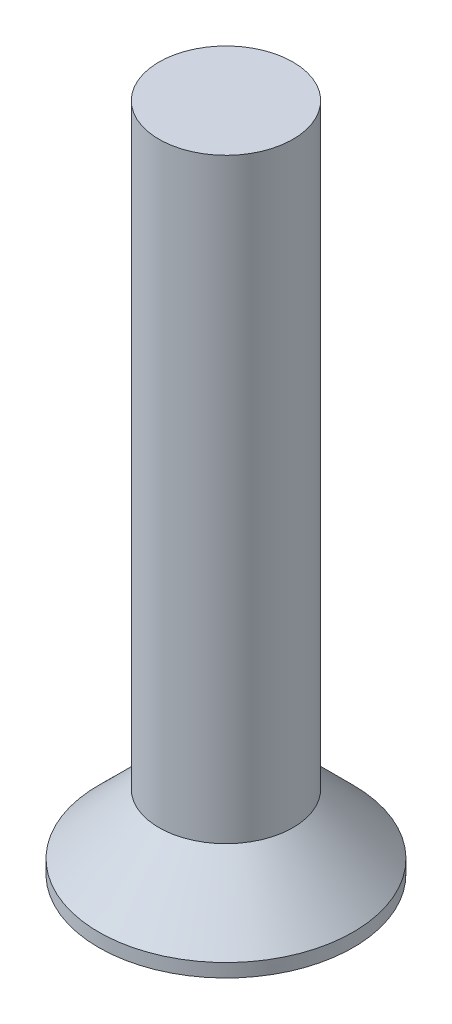
SolidWorks part; units mm, degrees
material "Nylon 101"
ref_plane "Front Plane" through (0, 0, 0) normal (0, 0, 1) x (1, 0, 0)
ref_plane "Top Plane" through (0, 0, 0) normal (0, 1, 0) x (1, 0, 0)
ref_plane "Right Plane" through (0, 0, 0) normal (1, 0, 0) x (0, 0, -1)
sketch "Sketch1" plane through (0, 0, 0) normal (0, 1, 0) x (1, 0, 0)
  circle A0 centre (0, 0) radius 1.9
  dimension "D1" = 3.8
extrude "Boss-Extrude1" add sketch "Sketch1" along normal blind 1.3
sketch "Sketch2" plane through (0, 0, 0) normal (0, -1, 0) x (1, 0, 0)
  circle A0 centre (0, 0) radius 1
  dimension "D1" = 2
extrude "Boss-Extrude2" add sketch "Sketch2" against normal blind 10
chamfer "Chamfer1" distance 1.1 angle 45 1 edges at (0, 1.3, 1.9)
sketch "Sketch3" plane through (0, 0, 0) normal (0, -1, 0) x (1, 0, 0)
  line L0 (-0.25, 1.5) -> (-0.25, 0.25)
  line L1 (1.5, -0.25) -> (-1.5, -0.25) construction
  line L2 (1.5, -0.25) -> (1.5, 0.25) construction
  line L3 (1.5, 0.25) -> (-1.5, 0.25) construction
  line L4 (-1.5, -0.25) -> (-1.5, 0.25) construction
  line L5 (1.5, -0.25) -> (-1.5, 0.25) construction
  line L6 (1.5, 0.25) -> (-1.5, -0.25) construction
  line L7 (-0.25, -1.5) -> (0.25, -1.5) construction
  line L8 (-0.25, -1.5) -> (-0.25, 1.5) construction
  line L9 (-0.25, 1.5) -> (0.25, 1.5) construction
  line L10 (0.25, -1.5) -> (0.25, 1.5) construction
  line L11 (-0.25, -1.5) -> (0.25, 1.5) construction
  line L12 (-0.25, 1.5) -> (0.25, -1.5) construction
  line L13 (-0.25, 0.25) -> (-1.5, 0.25)
  line L14 (-1.5, 0.25) -> (-1.5, -0.25)
  line L15 (-1.5, -0.25) -> (-0.25, -0.25)
  line L16 (-0.25, -0.25) -> (-0.25, -1.5)
  line L17 (-0.25, -1.5) -> (0.25, -1.5)
  line L18 (0.25, -1.5) -> (0.25, -0.25)
  line L19 (0.25, -0.25) -> (1.5, -0.25)
  line L20 (1.5, -0.25) -> (1.5, 0.25)
  line L21 (1.5, 0.25) -> (0.25, 0.25)
  line L22 (0.25, 0.25) -> (0.25, 1.5)
  line L23 (-0.25, 1.5) -> (0.25, 1.5)
  point P0 (0, 0)
  point P6 (0, 0)
  dimension "D1" = 3
  dimension "D2" = 0.5
extrude "Cut-Extrude1" cut sketch "Sketch3" against normal blind 0.3
